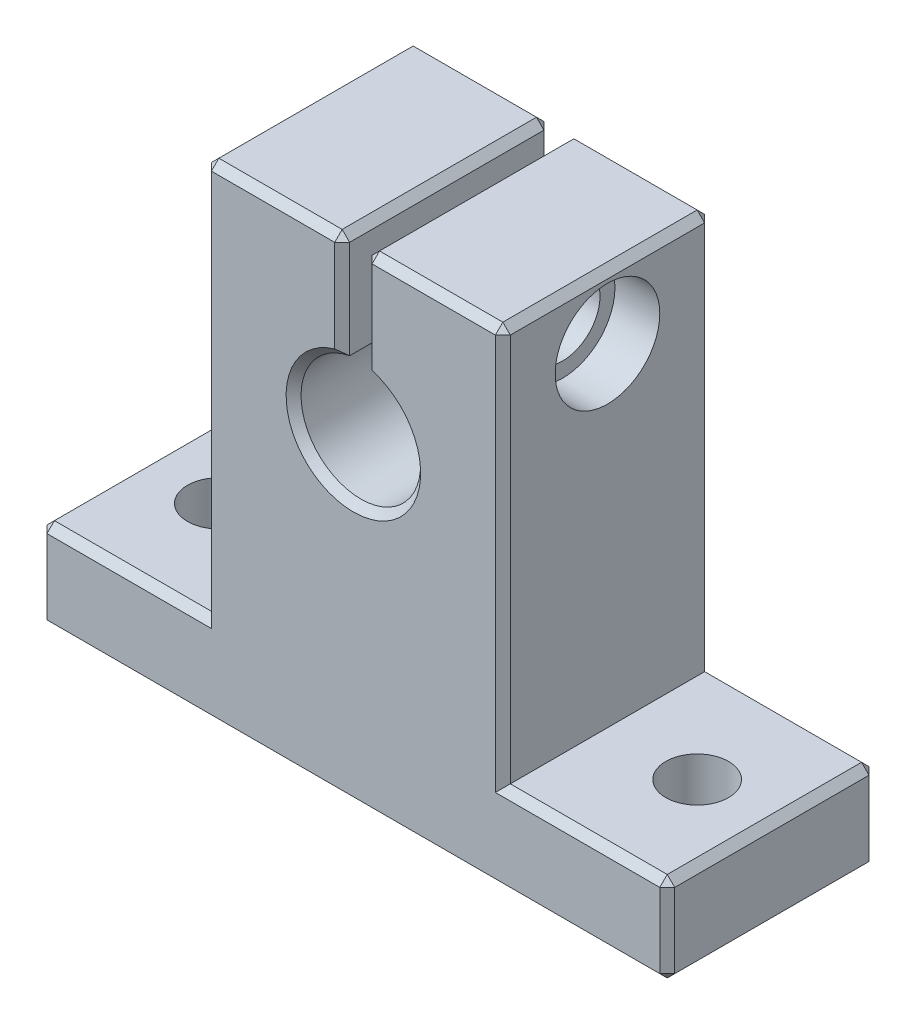
SolidWorks part; units mm, degrees
material "1060 Alloy"
ref_plane "Front Plane" through (0, 0, 0) normal (0, 0, 1) x (1, 0, 0)
ref_plane "Top Plane" through (0, 0, 0) normal (0, 1, 0) x (1, 0, 0)
ref_plane "Right Plane" through (0, 0, 0) normal (1, 0, 0) x (0, 0, -1)
sketch "Sketch1" plane through (0, 0, 0) normal (0, 0, 1) x (1, 0, 0)
  line L0 (-10, 11) -> (-0.75, 11)
  line L1 (10, 11) -> (10, -15.5)
  line L2 (10, -15.5) -> (21, -15.5)
  line L3 (21, -15.5) -> (21, -21.5)
  line L4 (21, -21.5) -> (-21, -21.5)
  line L5 (-21, -21.5) -> (-21, -15.5)
  line L6 (-21, -15.5) -> (-10, -15.5)
  line L7 (-10, -15.5) -> (-10, 11)
  line L8 (0, -21.5) -> (0, -4) construction
  line L9 (0, -4) -> (0, 0) construction
  line L10 (16, -15.5) -> (16, -21.5) construction
  line L11 (-16, -15.5) -> (-16, -21.5) construction
  line L12 (-16, -18.5) -> (0, -18.5) construction
  line L13 (0, -18.5) -> (16, -18.5) construction
  line L14 (0, 0) -> (0, 4) construction
  line L15 (0, 4) -> (0, 11) construction
  line L16 (0.75, 11) -> (0.75, 3.9291)
  line L17 (-0.75, 11) -> (-0.75, 3.9291)
  line L18 (0.75, 11) -> (10, 11)
  line L19 (-0.75, 11) -> (0, 11) construction
  line L20 (0, 11) -> (0.75, 11) construction
  line L21 (10, 7.2984) -> (-10, 7.2984) construction
  arc A0 (-0.75, 3.9291) -> (0.75, 3.9291) centre (0, 0) ccw
  dimension "D1" = 8
  dimension "D2" = 42
  dimension "D3" = 6
  dimension "D4" = 21.5
  dimension "D5" = 20
  dimension "D6" = 32.5
  dimension "D7" = 32
  dimension "D8" = 1.5
extrude "Body" add sketch "Sketch1" along normal mid plane 14
sketch "Sketch2" plane through (0, 0, 0) normal (1, 0, 0) x (0, 0, -1)
  line L0 (0, 0) -> (0, 4.25) construction
  line L1 (0, 4.25) -> (0, 6.75) construction
  line L2 (0, 6.75) -> (0, 9.25) construction
  line L3 (0, 9.25) -> (0, 11) construction
  line L4 (-7, 11) -> (7, 11) construction
  circle A0 centre (0, 6.75) radius 2.5
  dimension "D1" = 5
  dimension "D2" = 4.25
extrude "Bolt Clearance" cut sketch "Sketch2" along normal through all
sketch "Sketch3" plane through (10, 0, 0) normal (1, 0, 0) x (0, 0, -1)
  circle A0 centre (0, 6.75) radius 2.5 construction
  circle A1 centre (0, 6.75) radius 2.5 construction
  circle A2 centre (0, 6.75) radius 3.5
  dimension "D1" = 7
extrude "Bolt Head Seating" cut sketch "Sketch3" against normal blind 3
ref_axis "Bolt Axis" through (-0.0107, 6.75, 0) along (-1, 0, 0)
sketch "Clamping Hole Reference" plane through (-0.75, 0, 0) normal (1, 0, 0) x (0, 0, -1)
  line L0 (0, 6.75) -> (0, 9.25) construction
  circle A0 centre (0, 6.75) radius 2.5 construction
  circle A1 centre (0, 6.75) radius 2.5
hole_wizard "Clamping Hole (M4x0.7)" positions "3DSketch1" profile "Sketch5" tap size "M4x0.7" standard "ANSI Metric" end condition through all
sketch3d "3DSketch1"
  point P0 (-0.75, 6.75, 0)
sketch "Sketch5" plane through (-0.75, 6.75, 0) normal (0, 1, 0) x (0, 0, -1)
  line L0 (0, 0) -> (0, 20.25)
  line L1 (0, 20.25) -> (1.65, 20.25)
  line L2 (1.65, 20.25) -> (1.65, 0)
  line L5 (1.65, 0) -> (0, 0)
  line L11 (0, -6.35) -> (0, 107.95) construction
  dimension "Thru Tap Drill Dia." = 3.3
  dimension "Thru Tap Drill Depth" = 20.25
cosmetic thread "Hole Thread1" parameters "D2"=4
sketch "Mounting Hole Reference" plane through (0, -15.5, 0) normal (0, 1, 0) x (1, 0, 0)
  line L0 (-21, -7) -> (-21, 7) construction
  line L1 (-16, 0) -> (0, 0) construction
  line L2 (0, 0) -> (16, 0) construction
  circle A0 centre (-16, 0) radius 2.75
  circle A1 centre (16, 0) radius 2.75
  dimension "D2" = 5.5
  dimension "D1" = 5
hole_wizard "Mounting Hole (M5x0.8)" positions "3DSketch2" profile "Sketch8" tap size "M5x0.8" standard "ANSI Metric" end condition through all
sketch3d "3DSketch2"
  point P0 (-16, -15.5, 0)
  point P4 (16, -15.5, 0)
sketch "Sketch8" plane through (-16, -15.5, 0) normal (1, 0, 0) x (0, 0, 1)
  line L0 (0, 0) -> (0, 6)
  line L1 (0, 6) -> (2.1, 6)
  line L2 (2.1, 6) -> (2.1, 0)
  line L5 (2.1, 0) -> (0, 0)
  line L11 (0, -6.35) -> (0, 107.95) construction
  dimension "Thru Tap Drill Dia." = 4.2
  dimension "Thru Tap Drill Depth" = 6
cosmetic thread "Hole Thread2" parameters "D2"=5
cosmetic thread "Hole Thread3" parameters "D2"=5
chamfer "Chamfer" distance 0.5 angle 45 32 edges at (21, -21.5, 0) (21, -15.5, 0) (-21, -15.5, 0) (-21, -21.5, 0) (10, 11, 0) (0.75, 11, 0) (-0.75, 11, 0) (-15.5, -15.5, -7) (-21, -18.5, -7) (0, -21.5, -7) (21, -18.5, -7) (15.5, -15.5, -7) (10, -2.25, -7) (5.375, 11, -7) (0.75, 7.4645, -7) (0, -4, -7) (-0.75, 7.4645, -7) (-5.375, 11, -7) (-10, -2.25, -7) (-10, 11, 0) (-5.375, 11, 7) (-0.75, 7.4645, 7) (0, -4, 7) (0.75, 7.4645, 7) (5.375, 11, 7) (10, -2.25, 7) (15.5, -15.5, 7) (21, -18.5, 7) (0, -21.5, 7) (-21, -18.5, 7) (-15.5, -15.5, 7) (-10, -2.25, 7)
ref_axis "Shaft Axis" through (0, 0, 6.5) along (0, 0, -1)
